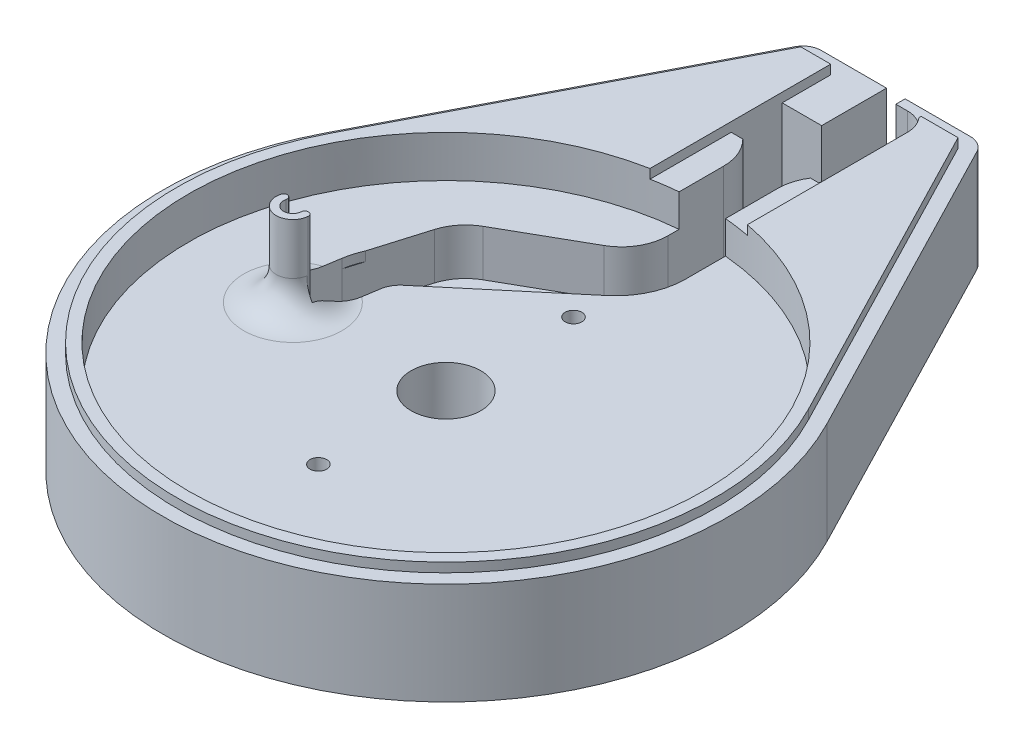
SolidWorks part; units mm, degrees
ref_plane "Front Plane" through (0, 0, 0) normal (0, 0, 1) x (1, 0, 0)
ref_plane "Top Plane" through (0, 0, 0) normal (0, 1, 0) x (1, 0, 0)
ref_plane "Right Plane" through (0, 0, 0) normal (1, 0, 0) x (0, 0, -1)
sketch "Sketch2" plane through (0, 0, 0) normal (0, 1, 0) x (1, 0, 0)
  line L0 (0, 0) -> (0, -50000) construction
  line L1 (-8.0329, 48.5) -> (8.0329, 48.5)
  line L2 (9.8092, 47.4189) -> (27.0899, 14.0138)
  line L5 (-9.8092, 47.4189) -> (-27.0899, 14.0138)
  arc A0 (-27.0899, 14.0138) -> (27.0899, 14.0138) centre (0, 0) ccw
  arc A1 (8.0329, 48.5) -> (9.8092, 47.4189) centre (8.0329, 46.5) cw
  arc A2 (-8.0329, 48.5) -> (-9.8092, 47.4189) centre (-8.0329, 46.5) ccw
  point P7 (0, 48.5)
  point P11 (9.25, 48.5)
  point P14 (-9.25, 48.5)
  line B0 (-2.0588, 15.568) -> (-3.3995, 1.8156) construction
  line B1 (-3.3995, 1.8156) -> (-6.3417, 1.8292) construction
  line B2 (-6.3582, -1.7708) -> (-3.4161, -1.7843) construction
  line B3 (-3.4161, -1.7843) -> (-2.2018, -15.5484) construction
  line B4 (2.0588, -15.568) -> (3.3995, -1.8156) construction
  line B5 (3.3995, -1.8156) -> (6.3417, -1.8292) construction
  line B6 (6.3582, 1.7708) -> (3.4161, 1.7843) construction
  line B7 (3.4161, 1.7843) -> (2.2018, 15.5484) construction
  circle B8 centre (0.0233, 5.0782) radius 0.5 construction
  circle B9 centre (0.0325, 7.0717) radius 0.5 construction
  circle B10 centre (0.0426, 9.2662) radius 0.5 construction
  circle B11 centre (0.0514, 11.1888) radius 0.5 construction
  circle B12 centre (0.0608, 13.2337) radius 0.5 construction
  circle B13 centre (0.07, 15.2218) radius 0.5 construction
  circle B14 centre (-6.8538, 0.0315) radius 0.5 construction
  circle B15 centre (-4.9129, 0.0226) radius 0.5 construction
  circle B16 centre (-0.07, -15.2218) radius 0.5 construction
  circle B17 centre (-0.0608, -13.2337) radius 0.5 construction
  circle B18 centre (-0.0514, -11.1888) radius 0.5 construction
  circle B19 centre (-0.0426, -9.2662) radius 0.5 construction
  circle B20 centre (-0.0325, -7.0717) radius 0.5 construction
  circle B21 centre (-0.0233, -5.0782) radius 0.5 construction
  circle B22 centre (4.9129, -0.0226) radius 0.5 construction
  circle B23 centre (6.8538, -0.0315) radius 0.5 construction
  circle B24 centre (0, 0) radius 3.4 construction
  arc B25 (-6.3417, 1.8292) -> (-6.3582, -1.7708) centre (-6.3499, 0.0292) ccw construction
  arc B26 (-2.2018, -15.5484) -> (2.0588, -15.568) centre (-0.0706, -15.3604) ccw construction
  arc B27 (6.3417, -1.8292) -> (6.3582, 1.7708) centre (6.3499, -0.0292) ccw construction
  arc B28 (2.2018, 15.5484) -> (-2.0588, 15.568) centre (0.0706, 15.3604) ccw construction
  line B29 (3.5517, -15.7135) -> (4.7598, -3.3219)
  line B30 (4.7598, -3.3219) -> (6.3348, -3.3292)
  line B31 (6.3651, 3.2708) -> (4.7901, 3.278)
  line B32 (4.7901, 3.278) -> (3.696, 15.6802)
  line B33 (-3.5517, 15.7135) -> (-4.7598, 3.3219)
  line B34 (-4.7598, 3.3219) -> (-6.3348, 3.3292)
  line B35 (-6.3651, -3.2708) -> (-4.7901, -3.278)
  line B36 (-4.7901, -3.278) -> (-3.696, -15.6802)
  arc B37 (-3.696, -15.6802) -> (3.5517, -15.7135) centre (-0.0706, -15.3604) ccw
  arc B38 (6.3348, -3.3292) -> (6.3651, 3.2708) centre (6.3499, -0.0292) ccw
  arc B39 (3.696, 15.6802) -> (-3.5517, 15.7135) centre (0.0706, 15.3604) ccw
  arc B40 (-6.3348, 3.3292) -> (-6.3651, -3.2708) centre (-6.3499, 0.0292) ccw
  circle B41 centre (-0.0608, -13.2337) radius 0.5
  circle B42 centre (0.0608, 13.2337) radius 0.5
  dimension "D1" = 61
  dimension "D4" = 2
  dimension "D2" = 48.5
  dimension "D3" = 18.5
sketch_block_instance "Block1-1"
sketch_block "Block1"
sketch_block_instance "Block1-1"
sketch_block "Block1" parameters "D1"=1.5
extrude "Boss-Extrude1" add sketch "Sketch2" along normal blind 4 contours L0 L1 A2 L5 A0 B37 B36 B35 B40 B34 B33 B39 | L1 L0 B39 B32 B31 B38 B30 B29 B37 A0 L2 A1 | B39 L0 B42 B41 B37 B29 B30 B38 B31 B32 | L0 B39 B33 B34 B40 B35 B36 B37 B41 B42 region at (-2.2175, 0, 17.7512) region at (-25.2018, 0, 15.3372)
sketch "Sketch4" plane through (0, 4, 0) normal (0, 1, 0) x (1, 0, 0)
  line L0 (0, 0) -> (0, 50000) construction
  line L2 (-5.25, 41.5) -> (5.25, 41.5)
  line L3 (-5.25, 41.5) -> (-5.25, 36)
  line L5 (5.25, 41.5) -> (5.25, 36)
  line L6 (-8.0329, 48.5) -> (8.0329, 48.5) construction
  line L7 (-2, 34) -> (2, 34)
  line L8 (2, 34) -> (2, 36)
  line L9 (2, 36) -> (5.25, 36)
  line L10 (-5.25, 36) -> (-2, 36)
  line L11 (-2, 36) -> (-2, 34)
  point P10 (0, 41.5)
  point P13 (0, 34)
  dimension "D1" = 7
  dimension "D2" = 5.5
  dimension "D3" = 10.5
  dimension "D4" = 4
  dimension "D5" = 2
extrude "Cut-Extrude1" cut sketch "Sketch4" against normal through all both and the other way through all
sketch "Sketch5" plane through (0, 4, 0) normal (0, 1, 0) x (1, 0, 0)
  line L0 (0, 34) -> (0, 23.3315) construction
  line L1 (-2, 34) -> (2, 34) construction
  line L2 (-1.7861, 19.5013) -> (-13.7741, 9.4421) construction
  line L3 (-15.5, 6.3855) -> (-16.5, 0) construction
  line L4 (-2.5, 34) -> (-2.5, 23.3315)
  line L5 (-3.393, 21.4164) -> (-15.3811, 11.3572)
  line L6 (-17.9699, 6.7723) -> (-18.9699, 0.3868)
  line L7 (2.5, 34) -> (2.5, 23.3315)
  line L8 (-0.1791, 17.5862) -> (-12.1672, 7.527)
  line L9 (-13.0301, 5.9987) -> (-14.0301, -0.3868)
  arc A0 (-13.7741, 9.4421) -> (-15.5, 6.3855) centre (-10.5602, 5.6119) ccw construction
  arc A1 (0, 23.3315) -> (-1.7861, 19.5013) centre (-5, 23.3315) cw construction
  arc A2 (-2.5, 23.3315) -> (-3.393, 21.4164) centre (-5, 23.3315) cw
  arc A3 (-15.3811, 11.3572) -> (-17.9699, 6.7723) centre (-10.5602, 5.6119) ccw
  arc A4 (2.5, 23.3315) -> (-0.1791, 17.5862) centre (-5, 23.3315) cw
  arc A5 (-12.1672, 7.527) -> (-13.0301, 5.9987) centre (-10.5602, 5.6119) ccw
  arc A6 (-2.5, 34) -> (2.5, 34) centre (0, 34) cw
  arc A7 (-18.9699, 0.3868) -> (-14.0301, -0.3868) centre (-16.5, 0) ccw
  point P14 (0, 21)
  dimension "D4" = 5
  dimension "D1" = 16.5
  dimension "D2" = 130
  dimension "D3" = 13
  dimension "D7" = 15.5
  dimension "D5" = 2.5
  dimension "D6" = 2.5
extrude "Cut-Extrude2" cut sketch "Sketch5" against normal blind 4.5
chamfer "Chamfer2" distance 2 angle 33 2 edges at (2, 2, -36) (-2, 2, -36) first distance on face at (2, 2, -35.75) first distance on face at (-3.625, 2, -36)
fillet "Fillet2" radius 5 2 edges at (2.4164, 2, -34.6412) (-2.3271, 2, -34.9136)
sketch "Sketch6" plane through (0, 0, 0) normal (0, -1, 0) x (1, 0, 0)
  line L3 (-27.0899, -14.0138) -> (-9.8092, -47.4189)
  line L4 (-8.0329, -48.5) -> (8.0329, -48.5)
  line L5 (9.8092, -47.4189) -> (27.0899, -14.0138)
  line L6 (-27.0899, -14.0138) -> (-9.8092, -47.4189)
  line L7 (-8.0329, -48.5) -> (8.0329, -48.5)
  line L8 (9.8092, -47.4189) -> (27.0899, -14.0138)
  arc A3 (27.0899, -14.0138) -> (-27.0899, -14.0138) centre (0, 0) ccw
  arc A4 (-9.8092, -47.4189) -> (-8.0329, -48.5) centre (-8.0329, -46.5) ccw
  arc A5 (8.0329, -48.5) -> (9.8092, -47.4189) centre (8.0329, -46.5) ccw
  arc A6 (27.0899, -14.0138) -> (-27.0899, -14.0138) centre (0, 0) ccw
  arc A7 (-9.8092, -47.4189) -> (-8.0329, -48.5) centre (-8.0329, -46.5) ccw
  arc A8 (8.0329, -48.5) -> (9.8092, -47.4189) centre (8.0329, -46.5) ccw
  dimension "D1" = 0
extrude "Boss-Extrude2" add sketch "Sketch6" along normal blind 2
sketch "Sketch7" plane through (0, 4, 0) normal (0, 1, 0) x (1, 0, 0)
  circle A0 centre (0, 0) radius 27.75
  dimension "D1" = 55.5
extrude "Cut-Extrude3" cut sketch "Sketch7" against normal blind 3.5
sketch "Sketch9" plane through (0, 0, 0) normal (0, 1, 0) x (1, 0, 0)
  line L2 (3.2988, 36) -> (-4, 36)
  line L15 (2.5, 23.3315) -> (2.5, 33.2889)
  line L16 (2.5, 23.3315) -> (2.5, 33.2889)
  line L19 (-2.5, 32.4293) -> (-2.5, 23.3315)
  line L20 (-2.5, 32.4293) -> (-2.5, 23.3315)
  line L23 (3.2988, 36) -> (5.25, 36)
  line L24 (5.25, 36) -> (5.25, 41.5)
  line L25 (5.25, 41.5) -> (-5.25, 41.5)
  line L26 (-5.25, 41.5) -> (-5.25, 36)
  line L27 (-5.25, 36) -> (-4, 36)
  line L29 (-3.393, 21.4164) -> (-15.3811, 11.3572)
  line L30 (-17.9699, 6.7723) -> (-18.9699, 0.3868)
  line L35 (-14.0301, -0.3868) -> (-13.0301, 5.9987)
  line L36 (-12.1672, 7.527) -> (-0.1791, 17.5862)
  line L49 (-3.393, 21.4164) -> (-15.3811, 11.3572)
  line L50 (-17.9699, 6.7723) -> (-18.9699, 0.3868)
  line L55 (-14.0301, -0.3868) -> (-13.0301, 5.9987)
  line L56 (-12.1672, 7.527) -> (-0.1791, 17.5862)
  arc A7 (3.2988, 36) -> (2.5, 33.2889) centre (7.5, 33.2889) ccw
  arc A8 (3.2988, 36) -> (2.5, 33.2889) centre (7.5, 33.2889) ccw
  arc A9 (-2.5, 32.4293) -> (-4, 36) centre (-7.5, 32.4293) ccw
  arc A10 (-2.5, 32.4293) -> (-4, 36) centre (-7.5, 32.4293) ccw
  arc A16 (-3.393, 21.4164) -> (-2.5, 23.3315) centre (-5, 23.3315) ccw
  arc A17 (-15.3811, 11.3572) -> (-17.9699, 6.7723) centre (-10.5602, 5.6119) ccw
  arc A18 (-18.9699, 0.3868) -> (-14.0301, -0.3868) centre (-16.5, 0) ccw
  arc A23 (-12.1672, 7.527) -> (-13.0301, 5.9987) centre (-10.5602, 5.6119) ccw
  arc A24 (-0.1791, 17.5862) -> (2.5, 23.3315) centre (-5, 23.3315) ccw
  arc A30 (-3.393, 21.4164) -> (-2.5, 23.3315) centre (-5, 23.3315) ccw
  arc A31 (-15.3811, 11.3572) -> (-17.9699, 6.7723) centre (-10.5602, 5.6119) ccw
  arc A32 (-18.9699, 0.3868) -> (-14.0301, -0.3868) centre (-16.5, 0) ccw
  arc A37 (-12.1672, 7.527) -> (-13.0301, 5.9987) centre (-10.5602, 5.6119) ccw
  arc A38 (-0.1791, 17.5862) -> (2.5, 23.3315) centre (-5, 23.3315) ccw
  dimension "D1" = 0
extrude "Cut-Extrude5" cut sketch "Sketch9" against normal blind 0.5
sketch "Sketch10" plane through (0, 0.5, 0) normal (0, 1, 0) x (1, 0, 0)
  circle A0 centre (0.0608, 13.2337) radius 0.5
  circle A1 centre (0, 0) radius 3.75
  circle A2 centre (-0.0608, -13.2337) radius 0.5
  circle A3 centre (-0.0608, -13.2337) radius 0.5 construction
  circle A4 centre (0.0608, 13.2337) radius 0.5 construction
  dimension "D1" = 7.5
extrude "Cut-Extrude6" cut sketch "Sketch10" against normal through all both and the other way through all
sketch "Sketch13" plane through (0, -0.5, 0) normal (0, 1, 0) x (1, 0, 0)
  line L57 (1, 27.6372) -> (1, 36)
  line L58 (3.2988, 36) -> (-4, 36) construction
  line L59 (-1, 27.6372) -> (-1, 36)
  line L60 (3.2988, 36) -> (-4, 36) construction
  line L61 (1, 36) -> (1, 41.5)
  line L62 (5.25, 41.5) -> (-5.25, 41.5) construction
  line L63 (-1, 23.3315) -> (-1, 27.6372)
  line L64 (1, 27.6372) -> (1, 23.3315)
  line L65 (-14.4169, 10.2082) -> (-2.4288, 20.2674)
  line L66 (-17.488, 0.1547) -> (-16.488, 6.5402)
  line L67 (-1.1433, 18.7353) -> (-13.1314, 8.6761)
  line L68 (-14.512, 6.2308) -> (-15.512, -0.1547)
  line L69 (-1, 23.3315) -> (-1, 27.6372)
  line L70 (1, 27.6372) -> (1, 23.3315)
  line L71 (-14.4169, 10.2082) -> (-2.4288, 20.2674)
  line L72 (-17.488, 0.1547) -> (-16.488, 6.5402)
  line L73 (-1.1433, 18.7353) -> (-13.1314, 8.6761)
  line L74 (-14.512, 6.2308) -> (-15.512, -0.1547)
  line L75 (-1, 36) -> (-1, 41.5)
  line L76 (5.25, 41.5) -> (-5.25, 41.5) construction
  arc A50 (1, 41.5) -> (-1, 41.5) centre (0, 41.5) ccw
  arc A54 (-1.1433, 18.7353) -> (1, 23.3315) centre (-5, 23.3315) ccw
  arc A55 (-2.4288, 20.2674) -> (-1, 23.3315) centre (-5, 23.3315) ccw
  arc A56 (-14.4169, 10.2082) -> (-16.488, 6.5402) centre (-10.5602, 5.6119) ccw
  arc A57 (-13.1314, 8.6761) -> (-14.512, 6.2308) centre (-10.5602, 5.6119) ccw
  arc A58 (-17.488, 0.1547) -> (-15.512, -0.1547) centre (-16.5, 0) ccw
  arc A59 (-1.1433, 18.7353) -> (1, 23.3315) centre (-5, 23.3315) ccw
  arc A60 (-2.4288, 20.2674) -> (-1, 23.3315) centre (-5, 23.3315) ccw
  arc A61 (-14.4169, 10.2082) -> (-16.488, 6.5402) centre (-10.5602, 5.6119) ccw
  arc A62 (-13.1314, 8.6761) -> (-14.512, 6.2308) centre (-10.5602, 5.6119) ccw
  arc A63 (-17.488, 0.1547) -> (-15.512, -0.1547) centre (-16.5, 0) ccw
  dimension "D1" = 1.5
extrude "Cut-Extrude7" cut sketch "Sketch13" against normal blind 0.5 and the other way through all
sketch "Sketch14" plane through (0, 0, -48.5) normal (0, 0, -1) x (-1, 0, 0)
  circle A0 centre (0, 0) radius 1
  dimension "D1" = 2
extrude "Cut-Extrude8" cut sketch "Sketch14" against normal blind 10.5
sketch "Sketch15" plane through (0, 0, -48.5) normal (0, 0, -1) x (-1, 0, 0)
  line L0 (0, 0) -> (0, 4) construction
  line L1 (8.0329, 4) -> (-8.0329, 4) construction
  line L2 (-1, 0) -> (-1, 4)
  line L3 (1, 0) -> (1, 4)
  arc A0 (-1, 0) -> (1, 0) centre (0, 0) ccw
  arc A1 (1, 4) -> (-1, 4) centre (0, 4) ccw
  circle A2 centre (0, 0) radius 1 construction
  point P5 (0, 2)
extrude "Cut-Extrude9" cut sketch "Sketch15" against normal blind 10.5
sketch "Sketch17" plane through (0, -0.5, 0) normal (0, 1, 0) x (1, 0, 0)
  arc A0 (-17.488, 0.1547) -> (-15.512, -0.1547) centre (-16.5, 0) ccw construction
  arc A1 (-17.4688, 0.2478) -> (-15.5035, -0.0834) centre (-16.5, 0) ccw
  arc A2 (-18.2439, 0.446) -> (-14.7063, -0.15) centre (-16.5, 0) ccw
  arc A3 (-17.4688, 0.2478) -> (-18.2439, 0.446) centre (-17.8563, 0.3469) ccw
  arc A4 (-15.5035, -0.0834) -> (-14.7063, -0.15) centre (-15.1049, -0.1167) cw
  dimension "D1" = 0.8
extrude "Boss-Extrude6" add sketch "Sketch17" along normal blind 10
sketch "Sketch19" plane through (0, 0.5, 0) normal (0, 1, 0) x (1, 0, 0)
  line L0 (-17.488, 0.1547) -> (-18.9699, 0.3868)
  line L1 (-15.512, -0.1547) -> (-14.0301, -0.3868)
  line L2 (-14.0301, -0.3868) -> (-14.4943, -3.3507)
  line L3 (-14.4943, -3.3507) -> (-19.4341, -2.5771)
  line L4 (-19.4341, -2.5771) -> (-18.9699, 0.3868)
  arc A0 (-17.488, 0.1547) -> (-15.512, -0.1547) centre (-16.5, 0) ccw
  arc A3 (-17.488, 0.1547) -> (-15.512, -0.1547) centre (-16.5, 0) ccw construction
  arc A4 (-17.4688, 0.2478) -> (-15.5035, -0.0834) centre (-16.5, 0) ccw construction
  dimension "D1" = 3
extrude "Boss-Extrude7" add sketch "Sketch19" against normal up to surface (1.5 mm away) up to face at (-7.3062, -1, -18.628)
sketch "Sketch70" plane through (0, 4, 0) normal (0, 1, 0) x (1, 0, 0)
  line L0 (5.25, 41.5) -> (5.25, 44.5)
  line L1 (2.25, 47.5) -> (1, 47.5)
  line L2 (1, 41.5) -> (1, 48.5) construction
  line L3 (1, 47.5) -> (1, 41.5)
  line L4 (1, 41.5) -> (5.25, 41.5)
  line L5 (1, 48.5) -> (8.0329, 48.5) construction
  arc A0 (2.25, 47.5) -> (5.25, 44.5) centre (2.25, 44.5) cw
  dimension "D1" = 3
  dimension "D2" = 1
extrude "Cut-Extrude12" cut sketch "Sketch70" against normal up to surface (4 mm away) up to face at (3.1598, 0, -38.2)
sketch "Sketch72" plane through (0, 0.5, 0) normal (0, 1, 0) x (1, 0, 0)
  circle A0 centre (0.0608, 13.2337) radius 0.9
  circle A1 centre (-0.0608, -13.2337) radius 0.9
  dimension "D1" = 1.8
extrude "Cut-Extrude13" cut sketch "Sketch72" against normal through all both and the other way through all
sketch "Sketch73" plane through (0, 4, 0) normal (0, 1, 0) x (1, 0, 0)
  line L29 (8.4769, 46.7297) -> (4.2571, 46.7297)
  line L30 (-8.4769, 46.7297) -> (-5.25, 46.7297)
  line L31 (-25.7576, 13.3246) -> (-8.4769, 46.7297)
  line L32 (8.4769, 46.7297) -> (25.7576, 13.3246)
  line L33 (-25.7576, 13.3246) -> (-8.4769, 46.7297)
  line L34 (8.4769, 46.7297) -> (25.7576, 13.3246)
  line L35 (-5.25, 46.7297) -> (-5.25, 27.2489)
  line L36 (-5.25, 41.5) -> (-5.25, 36) construction
  line L37 (5.25, 44.5) -> (5.25, 27.2489)
  arc A21 (5.25, 44.5) -> (2.25, 47.5) centre (2.25, 44.5) ccw construction
  arc A22 (-25.7576, 13.3246) -> (25.7576, 13.3246) centre (0, 0) ccw
  arc A23 (-25.7576, 13.3246) -> (25.7576, 13.3246) centre (0, 0) ccw
  arc A24 (-2.5, 27.6372) -> (2.5, 27.6372) centre (0, 0) ccw construction
  arc A25 (5.25, 44.5) -> (4.2571, 46.7297) centre (2.25, 44.5) ccw
  arc A26 (-5.25, 27.2489) -> (5.25, 27.2489) centre (0, 0) ccw
  dimension "D1" = 1.5
extrude "Boss-Extrude11" add sketch "Sketch73" along normal blind 1
sketch "Sketch74" plane through (0, 5, 0) normal (0, 1, 0) x (1, 0, 0)
  line L0 (1, 48.5) -> (8.0329, 48.5) construction
  line L1 (4.5, 48.5) -> (-4.5, 48.5)
  line L2 (4.5, 48.5) -> (4.5, 34.27)
  line L3 (4.5, 34.27) -> (-4.5, 34.27)
  line L4 (-4.5, 48.5) -> (-4.5, 34.27)
  line L5 (0, 0) -> (0, -50000) construction
  point P9 (0, 48.5)
  dimension "D1" = 14.23
  dimension "D2" = 9
extrude "Cut-Extrude14" cut sketch "Sketch74" against normal blind 1
sketch "Sketch75" plane through (0, 0.5, 0) normal (0, 1, 0) x (1, 0, 0)
  circle A0 centre (-0.0608, -13.2337) radius 0.9
  circle A1 centre (0.0608, 13.2337) radius 0.9
  circle A2 centre (0.0608, 13.2337) radius 0.9 construction
  circle A3 centre (-0.0608, -13.2337) radius 0.9 construction
sketch "Sketch76" plane through (0, 0.5, 0) normal (0, 1, 0) x (1, 0, 0)
  circle A0 centre (-0.0608, -13.2337) radius 2.2526
  circle A1 centre (0.0608, 13.2337) radius 1.7318
extrude "Boss-Extrude12" add sketch "Sketch76" against normal up to surface (2.5 mm away) up to face at (0.0608, -2, -12.3337)
sketch "Sketch77" plane through (0, 0.5, 0) normal (0, 1, 0) x (1, 0, 0)
  line L0 (0, -13.75) -> (0, 13.75) construction
  circle A0 centre (0, -13.75) radius 0.9
  circle A1 centre (0, 13.75) radius 0.9
  circle A2 centre (0.0608, 13.2337) radius 0.9 construction
  point P5 (0, 0)
  dimension "D1" = 27.5
extrude "Cut-Extrude15" cut sketch "Sketch77" against normal through all both and the other way through all
sketch "Sketch78" plane through (0, -2, 0) normal (0, -1, 0) x (1, 0, 0)
  line L3 (-27.0899, -14.0138) -> (-9.8092, -47.4189)
  line L4 (-8.0329, -48.5) -> (8.0329, -48.5)
  line L5 (9.8092, -47.4189) -> (27.0899, -14.0138)
  line L6 (-27.0899, -14.0138) -> (-9.8092, -47.4189)
  line L7 (-8.0329, -48.5) -> (8.0329, -48.5)
  line L8 (9.8092, -47.4189) -> (27.0899, -14.0138)
  circle A1 centre (0, 0) radius 3.75
  circle A2 centre (0, 0) radius 3.75
  arc A3 (27.0899, -14.0138) -> (-27.0899, -14.0138) centre (0, 0) ccw
  arc A4 (-9.8092, -47.4189) -> (-8.0329, -48.5) centre (-8.0329, -46.5) ccw
  arc A5 (8.0329, -48.5) -> (9.8092, -47.4189) centre (8.0329, -46.5) ccw
  arc A6 (27.0899, -14.0138) -> (-27.0899, -14.0138) centre (0, 0) ccw
  arc A7 (-9.8092, -47.4189) -> (-8.0329, -48.5) centre (-8.0329, -46.5) ccw
  arc A8 (8.0329, -48.5) -> (9.8092, -47.4189) centre (8.0329, -46.5) ccw
  circle A9 centre (0, -13.75) radius 0.9
  circle A10 centre (0, -13.75) radius 0.9
  circle A11 centre (0, 13.75) radius 0.9
  circle A12 centre (0, 13.75) radius 0.9
  dimension "D1" = 0
  dimension "D2" = 0
  dimension "D3" = 0
  dimension "D4" = 0
extrude "Boss-Extrude13" add sketch "Sketch78" along normal blind 5
sketch "Sketch79" plane through (0, 0.5, 0) normal (0, 1, 0) x (1, 0, 0)
  line L0 (1, 47.5) -> (1, 48.5) construction
  line L1 (1, 48.5) -> (-1, 48.5) construction
  line L2 (-1, 48.5) -> (-1, 41.5) construction
  line L4 (-1, 41.5) -> (-5.25, 41.5) construction
  line L5 (-5.25, 41.5) -> (-5.25, 36) construction
  line L6 (-5.25, 36) -> (-4, 36) construction
  line L10 (3.2988, 36) -> (5.25, 36) construction
  line L11 (5.25, 36) -> (5.25, 44.5) construction
  line L12 (2.25, 47.5) -> (1, 47.5) construction
  line L15 (-16.488, 6.5402) -> (-17.488, 0.1547) construction
  line L16 (-15.512, -0.1547) -> (-14.512, 6.2308) construction
  line L19 (-18.9699, 0.3868) -> (-18.2783, 0.2785) construction
  line L24 (-2.5, 32.4293) -> (-2.5, 23.3315) construction
  line L26 (-17.9699, 6.7723) -> (-18.9699, 0.3868) construction
  line L27 (-14.7217, -0.2785) -> (-14.0301, -0.3868) construction
  line L28 (-14.0301, -0.3868) -> (-13.0301, 5.9987) construction
  line L29 (-12.1672, 7.527) -> (-0.1791, 17.5862) construction
  line L30 (2.5, 23.3315) -> (2.5, 33.2889) construction
  line L35 (1, 47.5) -> (1, 48.5)
  line L36 (1, 48.5) -> (-1, 48.5)
  line L37 (-1, 48.5) -> (-1, 41.5)
  line L39 (-1, 41.5) -> (-5.25, 41.5)
  line L40 (-5.25, 41.5) -> (-5.25, 36)
  line L41 (-5.25, 36) -> (-4, 36)
  line L45 (3.2988, 36) -> (5.25, 36)
  line L46 (5.25, 36) -> (5.25, 44.5)
  line L47 (2.25, 47.5) -> (1, 47.5)
  line L50 (-17.4564, 0.356) -> (-17.488, 0.1547)
  line L51 (-15.512, -0.1547) -> (-15.4882, -0.0024)
  line L54 (-18.9699, 0.3868) -> (-18.2783, 0.2785)
  line L59 (-2.5, 32.4293) -> (-2.5, 26.4293)
  line L61 (-17.9699, 6.7723) -> (-18.9699, 0.3868)
  line L62 (-14.7217, -0.2785) -> (-14.0301, -0.3868)
  line L63 (-14.0301, -0.3868) -> (-13.0301, 5.9987)
  line L64 (-12.1672, 7.527) -> (-0.1791, 17.5862)
  line L65 (2.5, 23.3315) -> (2.5, 33.2889)
  line L71 (-17.9699, 6.7723) -> (-15.6797, 14.4309)
  line L72 (-13.3608, 17.3448) -> (-5.0285, 22.0828)
  arc A0 (-15.6797, 14.4309) -> (-13.3608, 17.3448) centre (-10.8893, 12.9984) cw
  arc A2 (5.25, 44.5) -> (2.25, 47.5) centre (2.25, 44.5) ccw construction
  arc A7 (-17.488, 0.1547) -> (-15.512, -0.1547) centre (-16.5, 0) ccw construction
  arc A10 (-18.2439, 0.446) -> (-18.2783, 0.2785) centre (-16.5, 0) ccw construction
  arc A11 (-17.4564, 0.356) -> (-18.2439, 0.446) centre (-17.8563, 0.3469) ccw construction
  arc A14 (-2.5, 32.4293) -> (-4, 36) centre (-7.5, 32.4293) ccw construction
  arc A17 (-12.1672, 7.527) -> (-13.0301, 5.9987) centre (-10.5602, 5.6119) ccw construction
  arc A18 (-0.1791, 17.5862) -> (2.5, 23.3315) centre (-5, 23.3315) ccw construction
  arc A19 (3.2988, 36) -> (2.5, 33.2889) centre (7.5, 33.2889) ccw construction
  arc A22 (-14.7063, -0.15) -> (-15.4882, -0.0024) centre (-15.1049, -0.1167) ccw construction
  arc A23 (-14.7217, -0.2785) -> (-14.7063, -0.15) centre (-16.5, 0) ccw construction
  arc A26 (5.25, 44.5) -> (2.25, 47.5) centre (2.25, 44.5) ccw
  arc A31 (-17.488, 0.1547) -> (-15.512, -0.1547) centre (-16.5, 0) ccw
  arc A34 (-18.2439, 0.446) -> (-18.2783, 0.2785) centre (-16.5, 0) ccw
  arc A35 (-17.4564, 0.356) -> (-18.2439, 0.446) centre (-17.8563, 0.3469) ccw
  arc A38 (-2.5, 32.4293) -> (-4, 36) centre (-7.5, 32.4293) ccw
  arc A41 (-12.1672, 7.527) -> (-13.0301, 5.9987) centre (-10.5602, 5.6119) ccw
  arc A42 (-0.1791, 17.5862) -> (2.5, 23.3315) centre (-5, 23.3315) ccw
  arc A43 (3.2988, 36) -> (2.5, 33.2889) centre (7.5, 33.2889) ccw
  arc A46 (-14.7063, -0.15) -> (-15.4882, -0.0024) centre (-15.1049, -0.1167) ccw
  arc A47 (-14.7217, -0.2785) -> (-14.7063, -0.15) centre (-16.5, 0) ccw
  arc A48 (-5.0285, 22.0828) -> (-2.5, 26.4293) centre (-7.5, 26.4293) ccw
  point P7 (-2.5, 24.4293)
  point P13 (-15.1049, 16.3531)
  dimension "D2" = 5
  dimension "D4" = 5
  dimension "D1" = 6
  dimension "D3" = 10
extrude "Cut-Extrude16" cut sketch "Sketch79" against normal blind 5
fillet "Fillet18" radius 0.5 2 edges at (1, -4.5, -48) (-1, -4.5, -45)
sketch "Sketch80" plane through (0, 0, -48.5) normal (0, 0, -1) x (-1, 0, 0)
  line L0 (0, 0) -> (0, -3) construction
  circle A0 centre (0, -3) radius 2
  dimension "D1" = 4
  dimension "D2" = 3
extrude "Cut-Extrude17" cut sketch "Sketch80" against normal blind 10
fillet "Fillet19" radius 3.5 1 edges at (-16.7785, 0.5, 1.7783)
